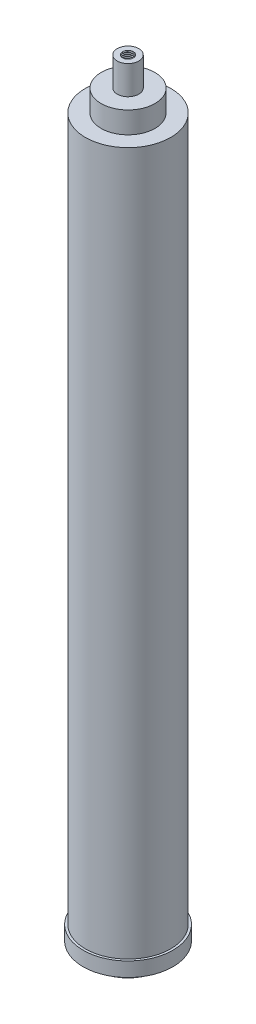
SolidWorks part; units mm, degrees
material "6061-T6 (SS)"
ref_plane "Front Plane" through (0, 0, 0) normal (0, 0, 1) x (1, 0, 0)
ref_plane "Top Plane" through (0, 0, 0) normal (0, 1, 0) x (1, 0, 0)
ref_plane "Right Plane" through (0, 0, 0) normal (1, 0, 0) x (0, 0, -1)
sketch "Sketch1" plane through (0, 0, 0) normal (0, 0, 1) x (1, 0, 0)
  line L0 (-37.6555, 0) -> (-39.6621, 0)
  line L1 (-37.6555, 0) -> (-37.6555, 621.03)
  line L2 (-37.6555, 621.03) -> (-23.8125, 621.03)
  line L3 (-23.8125, 621.03) -> (-23.8125, 640.08)
  line L4 (-23.8125, 640.08) -> (-9.525, 640.08)
  line L5 (-9.525, 640.08) -> (-9.525, 665.48)
  line L6 (-9.525, 665.48) -> (0, 665.48)
  line L7 (-39.6621, 0) -> (-39.6621, -12.7)
  line L8 (-39.6621, -12.7) -> (-27.94, -12.7)
  line L11 (0, 50.8) -> (0, 665.48)
  line L12 (0, 50.8) -> (-12.7, 50.8)
  line L13 (-12.7, 50.8) -> (-12.7, 25.4)
  line L14 (-12.7, 25.4) -> (-25.4, -21.336)
  line L15 (-25.4, -21.336) -> (-27.94, -21.336)
  line L16 (-23.8125, 621.03) -> (0, 621.03) construction
  line L17 (-37.6555, 1132.5688) -> (0, 1132.5688) construction
  line L18 (0, 50.8) -> (0, 0) construction
  line L19 (-39.6621, -12.7) -> (0, -12.7) construction
  line L20 (-12.7, 25.4) -> (-12.7, -12.7) construction
  line L21 (-27.94, -21.336) -> (-27.94, -12.7)
  dimension "D1" = 25.4
  dimension "D2" = 8.636
  dimension "D3" = 2.54
  dimension "D4" = 23.8125
  dimension "D5" = 37.6555
  dimension "D6" = 12.7
  dimension "D7" = 12.7
  dimension "D8" = 621.03
  dimension "D9" = 39.6621
  dimension "D10" = 38.1
  dimension "D11" = 25.4
  dimension "D12" = 44.45
  dimension "D13" = 27.94
  dimension "D14" = 9.525
revolve "Revolve1" add sketch "Sketch1" angle 360 about L11
hole_wizard "3/8 (0.375) Diameter Hole1" positions "Sketch6" profile "Sketch7" hole size "3/8" standard "ANSI Inch"
sketch "Sketch6" plane through (0, 665.48, 0) normal (0, 1, 0) x (1, 0, 0)
  point P0 (0, 0)
sketch "Sketch7" plane through (0, 665.48, 0) normal (1, 0, 0) x (0, 0, 1)
  line L0 (0, 0) -> (0, 28.2616)
  line L1 (0, 28.2616) -> (4.7625, 25.4)
  line L2 (4.7625, 25.4) -> (4.7625, 0)
  line L5 (4.7625, 0) -> (0, 0)
  line L10 (0, 28.2616) -> (-4.7625, 25.4) construction
  line L11 (0, -6.35) -> (0, 107.95) construction
  dimension "Hole Dia." = 9.525
  dimension "Hole Depth" = 25.4
  dimension "Drill Angle" = 118
thread "Thread1" pitch 1.5875 method cut profile "Thread Profile2" start angle 0, offset 0, length 25.4, pitch 1.5875, diameter 9.525
ref_plane "Plane2" through (-4.7625, 665.48, 0) normal (0, 0, 1) x (-1, 0, 0)
sketch "Thread Profile2" plane through (-4.7625, 665.48, 0) normal (0, 0, 1) x (-1, 0, 0)
  line L0 (0, 0) -> (0, 1.5875) construction
  line L1 (0, 0) -> (0.8593, 0.4961)
  line L2 (0.8593, 0.4961) -> (0.8593, 0.6945)
  line L3 (0.8593, 0.6945) -> (0, 1.1906)
  line L4 (0.8593, 0.5953) -> (0, 0.5953) construction
  line L11 (0, 0) -> (0, 1.1906)
  point P2 (0, 0)
  dimension "Pitch" = 1.5875
  dimension "Profile_Angle" = 60
  dimension "Profile_Land" = 0.1984
  dimension "Profile_Height" = 0.8593
equation "\"Grains\" = 5"
equation "\"CaseLength\"= IIF ( \"Grains\" = 1 , 8.45 , IIF ( \"Grains\" = 2 , 13.78 , IIF ( \"Grains\" = 3 , 19.12 , IIF ( \"Grains\" = 4 , 24.45 , IIF ( \"Grains\" = 5 , 29.79 , IIF ( \"Grains\" = 6 , 35.12 , 40.46 ) ) ) ) ) )"
